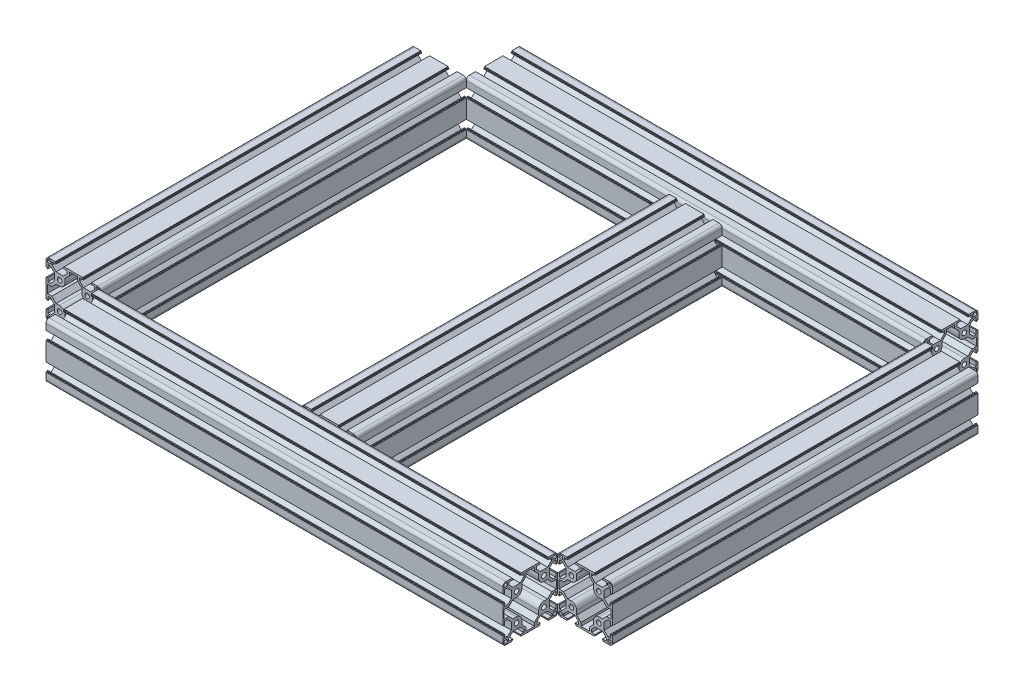
SolidWorks part; units mm, degrees
ref_plane "前视基准面" through (0, 0, 0) normal (0, 0, 1) x (1, 0, 0)
ref_plane "上视基准面" through (0, 0, 0) normal (0, 1, 0) x (1, 0, 0)
ref_plane "右视基准面" through (0, 0, 0) normal (1, 0, 0) x (0, 0, -1)
other "Configuration Table"
sketch "草图1" plane through (0, 0, 0) normal (0, 1, 0) x (1, 0, 0)
  line L0 (-260.7544, 120.2156) -> (239.2456, 120.2156)
  line L5 (-260.7544, 150.2156) -> (-260.7544, 90.2156)
  line L6 (-260.7544, 90.2156) -> (-320.7544, 90.2156)
  line L7 (239.2456, 150.2156) -> (239.2456, 90.2156)
  line L8 (239.2456, 90.2156) -> (299.2456, 90.2156)
  line L9 (-290.7544, 90.2156) -> (-290.7544, -309.7844)
  line L10 (-320.7544, -309.7844) -> (-260.7544, -309.7844)
  line L11 (-260.7544, -309.7844) -> (-260.7544, -369.7844)
  line L12 (-260.7544, -339.7844) -> (239.2456, -339.7844)
  line L13 (239.2456, -369.7844) -> (239.2456, -309.7844)
  line L14 (239.2456, -309.7844) -> (299.2456, -309.7844)
  line L15 (269.2456, -309.7844) -> (269.2456, 90.2156)
  line L16 (-10.7544, 90.2156) -> (-10.7544, -309.7844)
  dimension "D1" = 500
  dimension "D2" = 60
  dimension "D3" = 60
  dimension "D4" = 400
  dimension "D5" = 400
  dimension "D6" = 500
  dimension "D7" = 60
  dimension "D8" = 60
  dimension "D9" = 60
  dimension "D10" = 60
  dimension "D11" = 60
  dimension "D12" = 60
  dimension "D13" = 30
  dimension "D14" = 30
other "6060双槽 默认<按加工>(1)" corner treatment miter
ref_plane "基准面3" through (-290.7544, 0, -90.2156) normal (0, 0, 1) x (1, 0, 0)
sketch "草图110" plane through (-290.7544, 0, -90.2156) normal (0, 0, 1) x (1, 0, 0)
  line L2 (10.9, -29) -> (10.15, -29)
  line L3 (-9.1875, 15.1875) -> (-9.1875, 19.5636)
  line L4 (10.15, 30) -> (-10.15, 30)
  line L5 (-4.55, 28) -> (4.55, 28)
  line L6 (-11.0478, 20.8125) -> (-15, 20.8125)
  line L7 (-15, 20.8125) -> (-18.9522, 20.8125)
  line L8 (-18.9522, 20.8125) -> (-23.25, 25.1404)
  line L9 (-19.85, 30) -> (-26.625, 30)
  line L10 (-19.1, 29) -> (-19.85, 29)
  line L11 (-19.1, 28) -> (-23.25, 28)
  line L12 (-25.75, 28.6) -> (-27.6, 28.6)
  line L13 (-25.75, 25) -> (-27.6, 25)
  line L14 (-28.6, 27.6) -> (-28.6, 26)
  line L15 (-23.5575, 4.55) -> (-18.9522, 9.1875)
  line L16 (-18.9522, 9.1875) -> (-15.1875, 9.1875)
  line L17 (-19.85, 29) -> (-19.85, 30)
  line L18 (-9.1875, -19.5636) -> (-9.1875, -15.1875)
  line L19 (-15.1875, -9.1875) -> (-18.9522, -9.1875)
  line L20 (-28.5, 4.55) -> (-28.5, -4.55)
  line L21 (-23.5575, -4.55) -> (-18.9522, -9.1875)
  line L22 (9.1875, 15.1875) -> (9.1875, 19.5636)
  line L23 (23.5575, 4.55) -> (18.9522, 9.1875)
  line L24 (18.9522, 9.1875) -> (15.1875, 9.1875)
  line L25 (9.1875, -19.5636) -> (9.1875, -15.1875)
  line L26 (15.1875, -9.1875) -> (18.9522, -9.1875)
  line L27 (28.5, 4.55) -> (28.5, -4.55)
  line L28 (23.5575, -4.55) -> (18.9522, -9.1875)
  line L29 (-19.1, 29) -> (-19.1, 28)
  line L30 (-10.9, 29) -> (-10.15, 29)
  line L31 (-10.9, 28) -> (-6.75, 28)
  line L32 (-10.15, 29) -> (-10.15, 30)
  line L33 (-10.9, 29) -> (-10.9, 28)
  line L34 (-6.75, 28) -> (-6.75, 25.1404)
  line L35 (-4.55, 28) -> (-4.55, 24.2336)
  line L36 (-23.25, 28) -> (-23.25, 25.1404)
  line L37 (-24.75, 27.6) -> (-24.75, 26)
  line L38 (10.9, 29) -> (10.15, 29)
  line L39 (10.15, 29) -> (10.15, 30)
  line L40 (10.9, 29) -> (10.9, 28)
  line L41 (19.85, 30) -> (26.625, 30)
  line L42 (10.9, 28) -> (6.75, 28)
  line L43 (19.1, 29) -> (19.85, 29)
  line L44 (19.1, 28) -> (23.25, 28)
  line L45 (19.85, 29) -> (19.85, 30)
  line L46 (19.1, 29) -> (19.1, 28)
  line L47 (10.15, -30) -> (-10.15, -30)
  line L48 (-19.85, -30) -> (-26.625, -30)
  line L49 (-19.1, -29) -> (-19.85, -29)
  line L50 (-19.1, -28) -> (-23.6, -28)
  line L51 (-19.85, -29) -> (-19.85, -30)
  line L52 (-19.1, -29) -> (-19.1, -28)
  line L53 (-10.9, -29) -> (-10.15, -29)
  line L54 (-10.9, -28) -> (-7.1, -28)
  line L55 (-10.15, -29) -> (-10.15, -30)
  line L56 (-10.9, -29) -> (-10.9, -28)
  line L57 (10.15, -29) -> (10.15, -30)
  line L58 (10.9, -29) -> (10.9, -28)
  line L59 (19.85, -30) -> (26.625, -30)
  line L60 (10.9, -28) -> (7.1, -28)
  line L61 (19.1, -29) -> (19.85, -29)
  line L62 (19.1, -28) -> (23.6, -28)
  line L63 (19.85, -29) -> (19.85, -30)
  line L64 (19.1, -29) -> (19.1, -28)
  line L65 (-26, -28.6) -> (-27.6, -28.6)
  line L66 (-26, -25) -> (-27.6, -25)
  line L67 (-28.6, -27.6) -> (-28.6, -26)
  line L68 (-25, -27.6) -> (-25, -26)
  line L69 (26, -28.6) -> (27.6, -28.6)
  line L70 (26, -25) -> (27.6, -25)
  line L71 (28.6, -27.6) -> (28.6, -26)
  line L72 (25, -27.6) -> (25, -26)
  line L73 (-7.1, -24.7879) -> (-11.0478, -20.8125)
  line L74 (-11.0478, -20.8125) -> (-15, -20.8125)
  line L75 (-15, -20.8125) -> (-18.9522, -20.8125)
  line L76 (-18.9522, -20.8125) -> (-23.6, -25.4928)
  line L77 (-23.6, -28) -> (-23.6, -25.4928)
  line L78 (-7.1, -28) -> (-7.1, -24.7879)
  line L79 (7.1, -24.7879) -> (11.0478, -20.8125)
  line L80 (11.0478, -20.8125) -> (15, -20.8125)
  line L81 (15, -20.8125) -> (18.9522, -20.8125)
  line L82 (18.9522, -20.8125) -> (23.6, -25.4928)
  line L83 (23.6, -28) -> (23.6, -25.4928)
  line L84 (7.1, -28) -> (7.1, -24.7879)
  line L85 (-11.0478, 20.8125) -> (-6.75, 25.1404)
  line L86 (-9.1875, 19.5636) -> (-4.55, 24.2336)
  line L87 (11.0478, 20.8125) -> (15, 20.8125)
  line L88 (15, 20.8125) -> (18.9522, 20.8125)
  line L89 (18.9522, 20.8125) -> (23.25, 25.1404)
  line L90 (6.75, 28) -> (6.75, 25.1404)
  line L91 (4.55, 28) -> (4.55, 24.2336)
  line L92 (23.25, 28) -> (23.25, 25.1404)
  line L93 (11.0478, 20.8125) -> (6.75, 25.1404)
  line L94 (25.75, 28.6) -> (27.6, 28.6)
  line L95 (25.75, 25) -> (27.6, 25)
  line L96 (28.6, 27.6) -> (28.6, 26)
  line L97 (24.75, 27.6) -> (24.75, 26)
  line L98 (-30, 10.15) -> (-30, -10.15)
  line L99 (-20.8125, -11.0478) -> (-20.8125, -15)
  line L100 (-20.8125, -15) -> (-20.8125, -18.9522)
  line L101 (-20.8125, -18.9522) -> (-25.1404, -23.25)
  line L102 (-30, -19.85) -> (-30, -26.625)
  line L103 (-29, -19.1) -> (-29, -19.85)
  line L104 (-28, -19.1) -> (-28, -23.25)
  line L105 (-29, -19.85) -> (-30, -19.85)
  line L106 (-29, -10.9) -> (-29, -10.15)
  line L107 (-28, -10.9) -> (-28, -6.75)
  line L108 (-29, -10.15) -> (-30, -10.15)
  line L109 (-29, -10.9) -> (-28, -10.9)
  line L110 (-28, -6.75) -> (-25.1404, -6.75)
  line L111 (-28.5, -4.55) -> (-23.5575, -4.55)
  line L112 (-28, -23.25) -> (-25.1404, -23.25)
  line L113 (-29, 10.9) -> (-29, 10.15)
  line L114 (-29, 10.15) -> (-30, 10.15)
  line L115 (-29, 10.9) -> (-28, 10.9)
  line L116 (-30, 19.85) -> (-30, 26.625)
  line L117 (-28, 10.9) -> (-28, 6.75)
  line L118 (-29, 19.1) -> (-29, 19.85)
  line L119 (-28, 19.1) -> (-28, 23.25)
  line L120 (-29, 19.85) -> (-30, 19.85)
  line L121 (-29, 19.1) -> (-28, 19.1)
  line L122 (-20.8125, -11.0478) -> (-25.1404, -6.75)
  line L123 (-20.8125, 11.0478) -> (-20.8125, 15)
  line L124 (-20.8125, 15) -> (-20.8125, 18.9522)
  line L125 (-20.8125, 18.9522) -> (-25.1404, 23.25)
  line L126 (-28, 6.75) -> (-25.1404, 6.75)
  line L127 (-28.5, 4.55) -> (-23.5575, 4.55)
  line L128 (-28, 23.25) -> (-25.1404, 23.25)
  line L129 (-20.8125, 11.0478) -> (-25.1404, 6.75)
  line L130 (-29, -19.1) -> (-28, -19.1)
  line L131 (30, 10.15) -> (30, -10.15)
  line L132 (20.8125, -11.0478) -> (20.8125, -15)
  line L133 (20.8125, -15) -> (20.8125, -18.9522)
  line L134 (20.8125, -18.9522) -> (25.1404, -23.25)
  line L135 (30, -19.85) -> (30, -26.625)
  line L136 (29, -19.1) -> (29, -19.85)
  line L137 (28, -19.1) -> (28, -23.25)
  line L138 (29, -19.85) -> (30, -19.85)
  line L139 (29, -10.9) -> (29, -10.15)
  line L140 (28, -10.9) -> (28, -6.75)
  line L141 (29, -10.15) -> (30, -10.15)
  line L142 (29, -10.9) -> (28, -10.9)
  line L143 (28, -6.75) -> (25.1404, -6.75)
  line L144 (28.5, -4.55) -> (23.5575, -4.55)
  line L145 (28, -23.25) -> (25.1404, -23.25)
  line L146 (29, 10.9) -> (29, 10.15)
  line L147 (29, 10.15) -> (30, 10.15)
  line L148 (29, 10.9) -> (28, 10.9)
  line L149 (30, 19.85) -> (30, 26.625)
  line L150 (28, 10.9) -> (28, 6.75)
  line L151 (29, 19.1) -> (29, 19.85)
  line L152 (28, 19.1) -> (28, 23.25)
  line L153 (29, 19.85) -> (30, 19.85)
  line L154 (29, 19.1) -> (28, 19.1)
  line L155 (20.8125, -11.0478) -> (25.1404, -6.75)
  line L156 (20.8125, 11.0478) -> (20.8125, 15)
  line L157 (20.8125, 15) -> (20.8125, 18.9522)
  line L158 (20.8125, 18.9522) -> (25.1404, 23.25)
  line L159 (28, 6.75) -> (25.1404, 6.75)
  line L160 (28.5, 4.55) -> (23.5575, 4.55)
  line L161 (28, 23.25) -> (25.1404, 23.25)
  line L162 (20.8125, 11.0478) -> (25.1404, 6.75)
  line L163 (29, -19.1) -> (28, -19.1)
  line L164 (9.1875, 19.5636) -> (4.55, 24.2336)
  line L165 (-9.1875, -19.5636) -> (-4.55, -24.2336)
  line L166 (9.1875, -19.5636) -> (4.55, -24.2336)
  line L167 (-4.55, -28) -> (4.55, -28)
  line L168 (-4.55, -28) -> (-4.55, -24.2336)
  line L169 (4.55, -28) -> (4.55, -24.2336)
  arc A0 (-15.1875, 9.1875) -> (-9.1875, 15.1875) centre (-15.1875, 15.1875) ccw
  arc A2 (-27.6, 28.6) -> (-28.6, 27.6) centre (-27.6, 27.6) ccw
  arc A3 (-25.75, 25) -> (-24.75, 26) centre (-25.75, 26) ccw
  arc A4 (-30, -26.625) -> (-26.625, -30) centre (-26.625, -26.625) ccw
  arc A5 (-26.625, 30) -> (-30, 26.625) centre (-26.625, 26.625) ccw
  arc A6 (-28.6, 26) -> (-27.6, 25) centre (-27.6, 26) ccw
  circle A7 centre (-15, 15) radius 2.55
  arc A8 (-9.1875, -15.1875) -> (-15.1875, -9.1875) centre (-15.1875, -15.1875) ccw
  circle A9 centre (-15, -15) radius 2.55
  arc A10 (26.625, -30) -> (30, -26.625) centre (26.625, -26.625) ccw
  arc A11 (30, 26.625) -> (26.625, 30) centre (26.625, 26.625) ccw
  arc A12 (9.1875, 15.1875) -> (15.1875, 9.1875) centre (15.1875, 15.1875) ccw
  circle A13 centre (15, 15) radius 2.55
  arc A14 (15.1875, -9.1875) -> (9.1875, -15.1875) centre (15.1875, -15.1875) ccw
  circle A15 centre (15, -15) radius 2.55
  arc A16 (-24.75, 27.6) -> (-25.75, 28.6) centre (-25.75, 27.6) ccw
  arc A17 (-28.6, -27.6) -> (-27.6, -28.6) centre (-27.6, -27.6) ccw
  arc A18 (-25, -26) -> (-26, -25) centre (-26, -26) ccw
  arc A19 (-27.6, -25) -> (-28.6, -26) centre (-27.6, -26) ccw
  arc A20 (-26, -28.6) -> (-25, -27.6) centre (-26, -27.6) ccw
  arc A21 (27.6, -28.6) -> (28.6, -27.6) centre (27.6, -27.6) ccw
  arc A22 (26, -25) -> (25, -26) centre (26, -26) ccw
  arc A23 (28.6, -26) -> (27.6, -25) centre (27.6, -26) ccw
  arc A24 (25, -27.6) -> (26, -28.6) centre (26, -27.6) ccw
  arc A25 (28.6, 27.6) -> (27.6, 28.6) centre (27.6, 27.6) ccw
  arc A26 (24.75, 26) -> (25.75, 25) centre (25.75, 26) ccw
  arc A27 (27.6, 25) -> (28.6, 26) centre (27.6, 26) ccw
  arc A28 (25.75, 28.6) -> (24.75, 27.6) centre (25.75, 27.6) ccw
  point P0 (0, 0)
other "6060双槽 默认<按加工>(2)" corner treatment miter
ref_plane "基准面7" through (-10.7544, 0, -90.2156) normal (0, 0, 1) x (1, 0, 0)
sketch "草图111" plane through (-10.7544, 0, -90.2156) normal (0, 0, 1) x (1, 0, 0)
  line L2 (10.9, -29) -> (10.15, -29)
  line L3 (-9.1875, 15.1875) -> (-9.1875, 19.5636)
  line L4 (10.15, 30) -> (-10.15, 30)
  line L5 (-4.55, 28) -> (4.55, 28)
  line L6 (-11.0478, 20.8125) -> (-15, 20.8125)
  line L7 (-15, 20.8125) -> (-18.9522, 20.8125)
  line L8 (-18.9522, 20.8125) -> (-23.25, 25.1404)
  line L9 (-19.85, 30) -> (-26.625, 30)
  line L10 (-19.1, 29) -> (-19.85, 29)
  line L11 (-19.1, 28) -> (-23.25, 28)
  line L12 (-25.75, 28.6) -> (-27.6, 28.6)
  line L13 (-25.75, 25) -> (-27.6, 25)
  line L14 (-28.6, 27.6) -> (-28.6, 26)
  line L15 (-23.5575, 4.55) -> (-18.9522, 9.1875)
  line L16 (-18.9522, 9.1875) -> (-15.1875, 9.1875)
  line L17 (-19.85, 29) -> (-19.85, 30)
  line L18 (-9.1875, -19.5636) -> (-9.1875, -15.1875)
  line L19 (-15.1875, -9.1875) -> (-18.9522, -9.1875)
  line L20 (-28.5, 4.55) -> (-28.5, -4.55)
  line L21 (-23.5575, -4.55) -> (-18.9522, -9.1875)
  line L22 (9.1875, 15.1875) -> (9.1875, 19.5636)
  line L23 (23.5575, 4.55) -> (18.9522, 9.1875)
  line L24 (18.9522, 9.1875) -> (15.1875, 9.1875)
  line L25 (9.1875, -19.5636) -> (9.1875, -15.1875)
  line L26 (15.1875, -9.1875) -> (18.9522, -9.1875)
  line L27 (28.5, 4.55) -> (28.5, -4.55)
  line L28 (23.5575, -4.55) -> (18.9522, -9.1875)
  line L29 (-19.1, 29) -> (-19.1, 28)
  line L30 (-10.9, 29) -> (-10.15, 29)
  line L31 (-10.9, 28) -> (-6.75, 28)
  line L32 (-10.15, 29) -> (-10.15, 30)
  line L33 (-10.9, 29) -> (-10.9, 28)
  line L34 (-6.75, 28) -> (-6.75, 25.1404)
  line L35 (-4.55, 28) -> (-4.55, 24.2336)
  line L36 (-23.25, 28) -> (-23.25, 25.1404)
  line L37 (-24.75, 27.6) -> (-24.75, 26)
  line L38 (10.9, 29) -> (10.15, 29)
  line L39 (10.15, 29) -> (10.15, 30)
  line L40 (10.9, 29) -> (10.9, 28)
  line L41 (19.85, 30) -> (26.625, 30)
  line L42 (10.9, 28) -> (6.75, 28)
  line L43 (19.1, 29) -> (19.85, 29)
  line L44 (19.1, 28) -> (23.25, 28)
  line L45 (19.85, 29) -> (19.85, 30)
  line L46 (19.1, 29) -> (19.1, 28)
  line L47 (10.15, -30) -> (-10.15, -30)
  line L48 (-19.85, -30) -> (-26.625, -30)
  line L49 (-19.1, -29) -> (-19.85, -29)
  line L50 (-19.1, -28) -> (-23.6, -28)
  line L51 (-19.85, -29) -> (-19.85, -30)
  line L52 (-19.1, -29) -> (-19.1, -28)
  line L53 (-10.9, -29) -> (-10.15, -29)
  line L54 (-10.9, -28) -> (-7.1, -28)
  line L55 (-10.15, -29) -> (-10.15, -30)
  line L56 (-10.9, -29) -> (-10.9, -28)
  line L57 (10.15, -29) -> (10.15, -30)
  line L58 (10.9, -29) -> (10.9, -28)
  line L59 (19.85, -30) -> (26.625, -30)
  line L60 (10.9, -28) -> (7.1, -28)
  line L61 (19.1, -29) -> (19.85, -29)
  line L62 (19.1, -28) -> (23.6, -28)
  line L63 (19.85, -29) -> (19.85, -30)
  line L64 (19.1, -29) -> (19.1, -28)
  line L65 (-26, -28.6) -> (-27.6, -28.6)
  line L66 (-26, -25) -> (-27.6, -25)
  line L67 (-28.6, -27.6) -> (-28.6, -26)
  line L68 (-25, -27.6) -> (-25, -26)
  line L69 (26, -28.6) -> (27.6, -28.6)
  line L70 (26, -25) -> (27.6, -25)
  line L71 (28.6, -27.6) -> (28.6, -26)
  line L72 (25, -27.6) -> (25, -26)
  line L73 (-7.1, -24.7879) -> (-11.0478, -20.8125)
  line L74 (-11.0478, -20.8125) -> (-15, -20.8125)
  line L75 (-15, -20.8125) -> (-18.9522, -20.8125)
  line L76 (-18.9522, -20.8125) -> (-23.6, -25.4928)
  line L77 (-23.6, -28) -> (-23.6, -25.4928)
  line L78 (-7.1, -28) -> (-7.1, -24.7879)
  line L79 (7.1, -24.7879) -> (11.0478, -20.8125)
  line L80 (11.0478, -20.8125) -> (15, -20.8125)
  line L81 (15, -20.8125) -> (18.9522, -20.8125)
  line L82 (18.9522, -20.8125) -> (23.6, -25.4928)
  line L83 (23.6, -28) -> (23.6, -25.4928)
  line L84 (7.1, -28) -> (7.1, -24.7879)
  line L85 (-11.0478, 20.8125) -> (-6.75, 25.1404)
  line L86 (-9.1875, 19.5636) -> (-4.55, 24.2336)
  line L87 (11.0478, 20.8125) -> (15, 20.8125)
  line L88 (15, 20.8125) -> (18.9522, 20.8125)
  line L89 (18.9522, 20.8125) -> (23.25, 25.1404)
  line L90 (6.75, 28) -> (6.75, 25.1404)
  line L91 (4.55, 28) -> (4.55, 24.2336)
  line L92 (23.25, 28) -> (23.25, 25.1404)
  line L93 (11.0478, 20.8125) -> (6.75, 25.1404)
  line L94 (25.75, 28.6) -> (27.6, 28.6)
  line L95 (25.75, 25) -> (27.6, 25)
  line L96 (28.6, 27.6) -> (28.6, 26)
  line L97 (24.75, 27.6) -> (24.75, 26)
  line L98 (-30, 10.15) -> (-30, -10.15)
  line L99 (-20.8125, -11.0478) -> (-20.8125, -15)
  line L100 (-20.8125, -15) -> (-20.8125, -18.9522)
  line L101 (-20.8125, -18.9522) -> (-25.1404, -23.25)
  line L102 (-30, -19.85) -> (-30, -26.625)
  line L103 (-29, -19.1) -> (-29, -19.85)
  line L104 (-28, -19.1) -> (-28, -23.25)
  line L105 (-29, -19.85) -> (-30, -19.85)
  line L106 (-29, -10.9) -> (-29, -10.15)
  line L107 (-28, -10.9) -> (-28, -6.75)
  line L108 (-29, -10.15) -> (-30, -10.15)
  line L109 (-29, -10.9) -> (-28, -10.9)
  line L110 (-28, -6.75) -> (-25.1404, -6.75)
  line L111 (-28.5, -4.55) -> (-23.5575, -4.55)
  line L112 (-28, -23.25) -> (-25.1404, -23.25)
  line L113 (-29, 10.9) -> (-29, 10.15)
  line L114 (-29, 10.15) -> (-30, 10.15)
  line L115 (-29, 10.9) -> (-28, 10.9)
  line L116 (-30, 19.85) -> (-30, 26.625)
  line L117 (-28, 10.9) -> (-28, 6.75)
  line L118 (-29, 19.1) -> (-29, 19.85)
  line L119 (-28, 19.1) -> (-28, 23.25)
  line L120 (-29, 19.85) -> (-30, 19.85)
  line L121 (-29, 19.1) -> (-28, 19.1)
  line L122 (-20.8125, -11.0478) -> (-25.1404, -6.75)
  line L123 (-20.8125, 11.0478) -> (-20.8125, 15)
  line L124 (-20.8125, 15) -> (-20.8125, 18.9522)
  line L125 (-20.8125, 18.9522) -> (-25.1404, 23.25)
  line L126 (-28, 6.75) -> (-25.1404, 6.75)
  line L127 (-28.5, 4.55) -> (-23.5575, 4.55)
  line L128 (-28, 23.25) -> (-25.1404, 23.25)
  line L129 (-20.8125, 11.0478) -> (-25.1404, 6.75)
  line L130 (-29, -19.1) -> (-28, -19.1)
  line L131 (30, 10.15) -> (30, -10.15)
  line L132 (20.8125, -11.0478) -> (20.8125, -15)
  line L133 (20.8125, -15) -> (20.8125, -18.9522)
  line L134 (20.8125, -18.9522) -> (25.1404, -23.25)
  line L135 (30, -19.85) -> (30, -26.625)
  line L136 (29, -19.1) -> (29, -19.85)
  line L137 (28, -19.1) -> (28, -23.25)
  line L138 (29, -19.85) -> (30, -19.85)
  line L139 (29, -10.9) -> (29, -10.15)
  line L140 (28, -10.9) -> (28, -6.75)
  line L141 (29, -10.15) -> (30, -10.15)
  line L142 (29, -10.9) -> (28, -10.9)
  line L143 (28, -6.75) -> (25.1404, -6.75)
  line L144 (28.5, -4.55) -> (23.5575, -4.55)
  line L145 (28, -23.25) -> (25.1404, -23.25)
  line L146 (29, 10.9) -> (29, 10.15)
  line L147 (29, 10.15) -> (30, 10.15)
  line L148 (29, 10.9) -> (28, 10.9)
  line L149 (30, 19.85) -> (30, 26.625)
  line L150 (28, 10.9) -> (28, 6.75)
  line L151 (29, 19.1) -> (29, 19.85)
  line L152 (28, 19.1) -> (28, 23.25)
  line L153 (29, 19.85) -> (30, 19.85)
  line L154 (29, 19.1) -> (28, 19.1)
  line L155 (20.8125, -11.0478) -> (25.1404, -6.75)
  line L156 (20.8125, 11.0478) -> (20.8125, 15)
  line L157 (20.8125, 15) -> (20.8125, 18.9522)
  line L158 (20.8125, 18.9522) -> (25.1404, 23.25)
  line L159 (28, 6.75) -> (25.1404, 6.75)
  line L160 (28.5, 4.55) -> (23.5575, 4.55)
  line L161 (28, 23.25) -> (25.1404, 23.25)
  line L162 (20.8125, 11.0478) -> (25.1404, 6.75)
  line L163 (29, -19.1) -> (28, -19.1)
  line L164 (9.1875, 19.5636) -> (4.55, 24.2336)
  line L165 (-9.1875, -19.5636) -> (-4.55, -24.2336)
  line L166 (9.1875, -19.5636) -> (4.55, -24.2336)
  line L167 (-4.55, -28) -> (4.55, -28)
  line L168 (-4.55, -28) -> (-4.55, -24.2336)
  line L169 (4.55, -28) -> (4.55, -24.2336)
  arc A0 (-15.1875, 9.1875) -> (-9.1875, 15.1875) centre (-15.1875, 15.1875) ccw
  arc A2 (-27.6, 28.6) -> (-28.6, 27.6) centre (-27.6, 27.6) ccw
  arc A3 (-25.75, 25) -> (-24.75, 26) centre (-25.75, 26) ccw
  arc A4 (-30, -26.625) -> (-26.625, -30) centre (-26.625, -26.625) ccw
  arc A5 (-26.625, 30) -> (-30, 26.625) centre (-26.625, 26.625) ccw
  arc A6 (-28.6, 26) -> (-27.6, 25) centre (-27.6, 26) ccw
  circle A7 centre (-15, 15) radius 2.55
  arc A8 (-9.1875, -15.1875) -> (-15.1875, -9.1875) centre (-15.1875, -15.1875) ccw
  circle A9 centre (-15, -15) radius 2.55
  arc A10 (26.625, -30) -> (30, -26.625) centre (26.625, -26.625) ccw
  arc A11 (30, 26.625) -> (26.625, 30) centre (26.625, 26.625) ccw
  arc A12 (9.1875, 15.1875) -> (15.1875, 9.1875) centre (15.1875, 15.1875) ccw
  circle A13 centre (15, 15) radius 2.55
  arc A14 (15.1875, -9.1875) -> (9.1875, -15.1875) centre (15.1875, -15.1875) ccw
  circle A15 centre (15, -15) radius 2.55
  arc A16 (-24.75, 27.6) -> (-25.75, 28.6) centre (-25.75, 27.6) ccw
  arc A17 (-28.6, -27.6) -> (-27.6, -28.6) centre (-27.6, -27.6) ccw
  arc A18 (-25, -26) -> (-26, -25) centre (-26, -26) ccw
  arc A19 (-27.6, -25) -> (-28.6, -26) centre (-27.6, -26) ccw
  arc A20 (-26, -28.6) -> (-25, -27.6) centre (-26, -27.6) ccw
  arc A21 (27.6, -28.6) -> (28.6, -27.6) centre (27.6, -27.6) ccw
  arc A22 (26, -25) -> (25, -26) centre (26, -26) ccw
  arc A23 (28.6, -26) -> (27.6, -25) centre (27.6, -26) ccw
  arc A24 (25, -27.6) -> (26, -28.6) centre (26, -27.6) ccw
  arc A25 (28.6, 27.6) -> (27.6, 28.6) centre (27.6, 27.6) ccw
  arc A26 (24.75, 26) -> (25.75, 25) centre (25.75, 26) ccw
  arc A27 (27.6, 25) -> (28.6, 26) centre (27.6, 26) ccw
  arc A28 (25.75, 28.6) -> (24.75, 27.6) centre (25.75, 27.6) ccw
  point P0 (0, 0)
